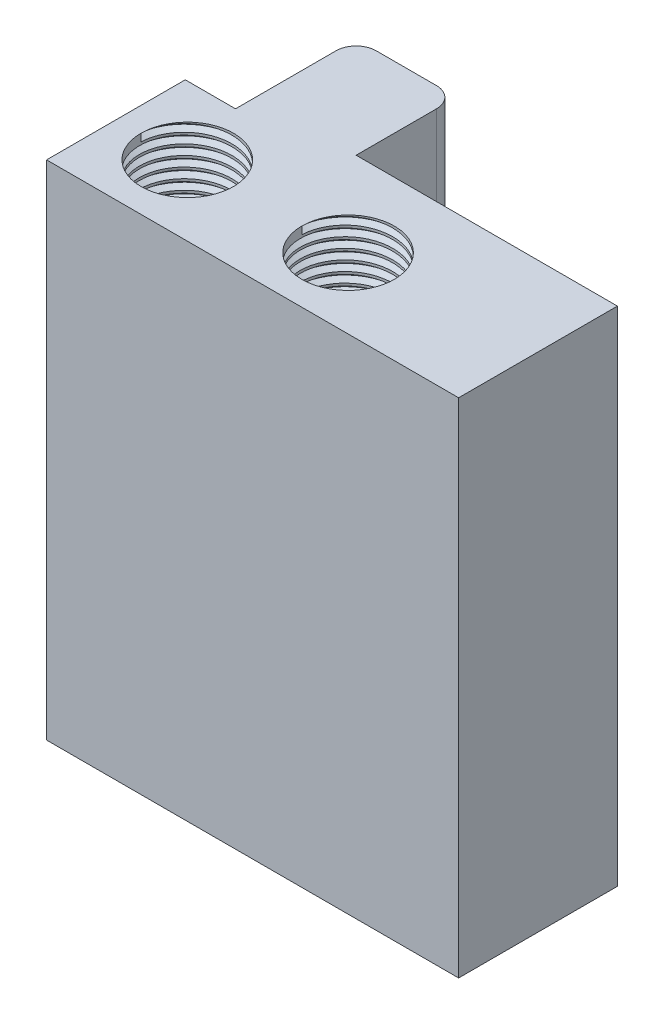
SolidWorks part; units mm, degrees
ref_plane "Front Plane" through (0, 0, 0) normal (0, 0, 1) x (1, 0, 0)
ref_plane "Top Plane" through (0, 0, 0) normal (0, 1, 0) x (1, 0, 0)
ref_plane "Right Plane" through (0, 0, 0) normal (1, 0, 0) x (0, 0, -1)
sketch "Sketch1" plane through (0, 0, 0) normal (0, 0, 1) x (1, 0, 0)
  line L1 (0, 0) -> (52.07, 0)
  line L2 (0, 0) -> (0, 63.5)
  line L3 (0, 63.5) -> (52.07, 63.5)
  line L4 (52.07, 0) -> (52.07, 63.5)
  dimension "D1" = 63.5
  dimension "D2" = 52.07
extrude "Boss-Extrude1" add sketch "Sketch1" along normal blind 20.066
sketch "Sketch2" plane through (0, 63.5, 0) normal (0, 1, 0) x (1, 0, 0)
  line L0 (0, -11.176) -> (52.07, -11.176) construction
  line L1 (52.07, -20.066) -> (0, -20.066) construction
  line L3 (0, -20.066) -> (0, 0) construction
  line L4 (52.07, -20.066) -> (52.07, 0) construction
  circle A0 centre (8.89, -11.176) radius 5.842
  circle A1 centre (29.21, -11.176) radius 5.842
  dimension "D1" = 11.684
  dimension "D2" = 11.684
  dimension "D3" = 8.89
  dimension "D4" = 8.89
  dimension "D5" = 29.21
extrude "Cut-Extrude1" cut sketch "Sketch2" against normal blind 50.8
thread "Thread1" pitch 1.27 method cut profile "Thread Profile1" start angle 0, offset 0, length 17.78, pitch 1.27, diameter 11.684
ref_plane "Plane4" through (3.048, 63.5, 11.176) normal (0, 0, 1) x (-1, 0, 0)
sketch "Thread Profile1" plane through (3.048, 63.5, 11.176) normal (0, 0, 1) x (-1, 0, 0)
  line L0 (0, 0) -> (0, 1.27) construction
  line L1 (0, 0) -> (0.6874, 0.3969)
  line L2 (0.6874, 0.3969) -> (0.6874, 0.5556)
  line L3 (0.6874, 0.5556) -> (0, 0.9525)
  line L4 (0.6874, 0.4762) -> (0, 0.4762) construction
  line L11 (0, 0) -> (0, 0.9525)
  point P2 (0, 0)
  dimension "Pitch" = 1.27
  dimension "Profile_Angle" = 60
  dimension "Profile_Land" = 0.1588
  dimension "Profile_Height" = 0.6874
thread "Thread2" pitch 1.27 method cut profile "Thread Profile2" start angle 0, offset 0, length 17.78, pitch 1.27, diameter 11.684
ref_plane "Plane5" through (23.368, 63.5, 11.176) normal (0, 0, 1) x (-1, 0, 0)
sketch "Thread Profile2" plane through (23.368, 63.5, 11.176) normal (0, 0, 1) x (-1, 0, 0)
  line L0 (0, 0) -> (0, 1.27) construction
  line L1 (0, 0) -> (0.6874, 0.3969)
  line L2 (0.6874, 0.3969) -> (0.6874, 0.5556)
  line L3 (0.6874, 0.5556) -> (0, 0.9525)
  line L4 (0.6874, 0.4762) -> (0, 0.4762) construction
  line L11 (0, 0) -> (0, 0.9525)
  point P2 (0, 0)
  dimension "Pitch" = 1.27
  dimension "Profile_Angle" = 60
  dimension "Profile_Land" = 0.1588
  dimension "Profile_Height" = 0.6874
sketch "Sketch3" plane through (0, 0, 0) normal (0, 0, -1) x (-1, 0, 0)
  line L0 (0, 63.5) -> (-6.35, 63.5)
  line L1 (-52.07, 63.5) -> (0, 63.5) construction
  line L2 (-6.35, 63.5) -> (-6.35, 0)
  line L3 (0, 0) -> (-52.07, 0) construction
  line L4 (-6.35, 0) -> (0, 0)
  line L5 (0, 0) -> (0, 63.5)
  dimension "D1" = 6.35
extrude "Cut-Extrude2" cut sketch "Sketch3" against normal blind 2.54
sketch "Sketch4" plane through (0, 0, 0) normal (0, 0, -1) x (-1, 0, 0)
  line L0 (-6.35, 31.75) -> (-52.07, 31.75) construction
  line L1 (-6.35, 63.5) -> (-6.35, 0) construction
  line L2 (-52.07, 0) -> (-52.07, 63.5) construction
  line L3 (-6.35, 63.5) -> (-6.35, 0) construction
  line L4 (-19.05, 0) -> (-6.35, 0)
  line L5 (-19.05, 0) -> (-19.05, 63.5)
  line L6 (-19.05, 63.5) -> (-6.35, 63.5)
  line L7 (-6.35, 0) -> (-6.35, 63.5)
  line L8 (-12.7, 63.5) -> (-12.7, 0) construction
  line L9 (-19.05, 31.75) -> (-6.35, 31.75) construction
  line L10 (-6.35, 0) -> (-52.07, 0) construction
  point P6 (-12.7, 31.75)
  dimension "D2" = 12.7
extrude "Boss-Extrude2" add sketch "Sketch4" along normal blind 12.7
sketch "Sketch6" plane through (19.05, 0, 0) normal (1, 0, 0) x (0, 0, -1)
  line L0 (6.35, 63.5) -> (6.35, 0) construction
  line L1 (12.7, 63.5) -> (0, 63.5) construction
  line L2 (12.7, 0) -> (0, 0) construction
  circle A0 centre (6.35, 31.75) radius 4.699
  dimension "D1" = 9.398
extrude "Cut-Extrude3" cut sketch "Sketch6" against normal blind 10.16
fillet "Fillet1" radius 2.54 2 edges at (19.05, 31.75, -12.7) (6.35, 31.75, -12.7)
